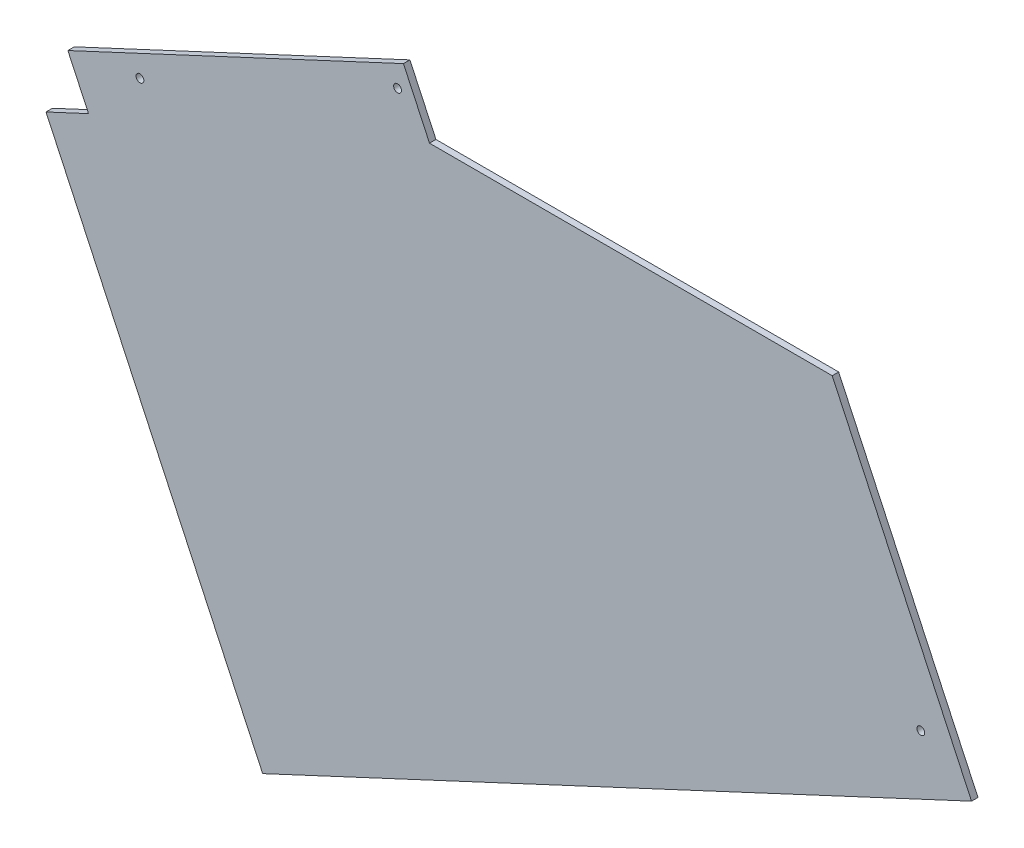
SolidWorks part; units mm, degrees
ref_plane "Front Plane" through (0, 0, 0) normal (0, 0, 1) x (1, 0, 0)
ref_plane "Top Plane" through (0, 0, 0) normal (0, 1, 0) x (1, 0, 0)
ref_plane "Right Plane" through (0, 0, 0) normal (1, 0, 0) x (0, 0, -1)
sketch "Sketch1" plane through (0, 0, 0) normal (0, 0, 1) x (1, 0, 0)
  line L0 (327.4362, 0.0035) -> (121.4984, 0.0035)
  line L1 (121.4984, 0.0035) -> (108.169, 28.5884)
  line L2 (108.169, 28.5884) -> (-63.4467, -51.4373)
  line L3 (-63.4467, -51.4373) -> (57.9293, -311.7289) construction
  line L4 (57.9293, -311.7289) -> (398.701, -152.8244)
  line L5 (271.5352, 119.8836) -> (277.3251, 107.4672) construction
  line L6 (190.5834, 136.311) -> (-12.0446, 41.824) construction
  line L7 (-63.4467, -51.4373) -> (255.5737, 97.3243) construction
  line L8 (398.701, -152.8244) -> (327.4362, 0.0035)
  line L9 (57.9293, -311.7289) -> (36.1779, -321.8717)
  line L10 (36.1779, -321.8717) -> (-74.6326, -84.2378)
  line L11 (50.7481, 0) -> (323.7481, 0) construction
  line L12 (-74.6326, -84.2378) -> (-52.8812, -74.095)
  line L13 (-90.9879, -49.1637) -> (-85.1981, -61.5801) construction
  line L14 (-52.8812, -74.095) -> (-63.4467, -51.4373)
  circle A0 centre (162.7613, -40.6644) radius 32.5 construction
  circle A1 centre (336.0773, -108.8767) radius 32.5 construction
  circle A2 centre (90.1802, -40.6644) radius 32.5 construction
  circle A3 centre (232.5481, -40.6644) radius 32.5 construction
  circle A4 centre (207.2768, 100.5118) radius 39.5 construction
  arc A5 (-3.3339, 41.4724) -> (-17.3744, 34.9252) centre (-8.0297, 33.2141) ccw construction
  circle A6 centre (304.5287, -40.6644) radius 32.5 construction
  circle A7 centre (254.9584, -108.8767) radius 32.5 construction
  circle A8 centre (179.3206, -108.8767) radius 32.5 construction
  circle A9 centre (101.4264, -108.8767) radius 32.5 construction
  circle A10 centre (270.383, -163.8108) radius 32.5 construction
  circle A11 centre (372.7594, -134.5783) radius 2
  dimension "D2" = 65
  dimension "D3" = 65
  dimension "D5" = 4
  dimension "D1" = 350
  dimension "D4" = 25
  dimension "24.5/2" = 15.8
  dimension "D6" = 27.5
extrude "Boss-Extrude1" add sketch "Sketch1" along normal up to surface (3.3 mm away)
sketch "Sketch2" plane through (0, 0, 3.3) normal (0, 0, 1) x (1, 0, 0)
  circle A0 centre (105.1447, 16.1444) radius 2
  circle A1 centre (-26.5934, -45.2861) radius 2
  circle A2 centre (-26.5934, -45.2861) radius 2 construction
  circle A3 centre (105.1447, 16.1444) radius 2 construction
extrude "Cut-Extrude1" cut sketch "Sketch2" against normal through all
